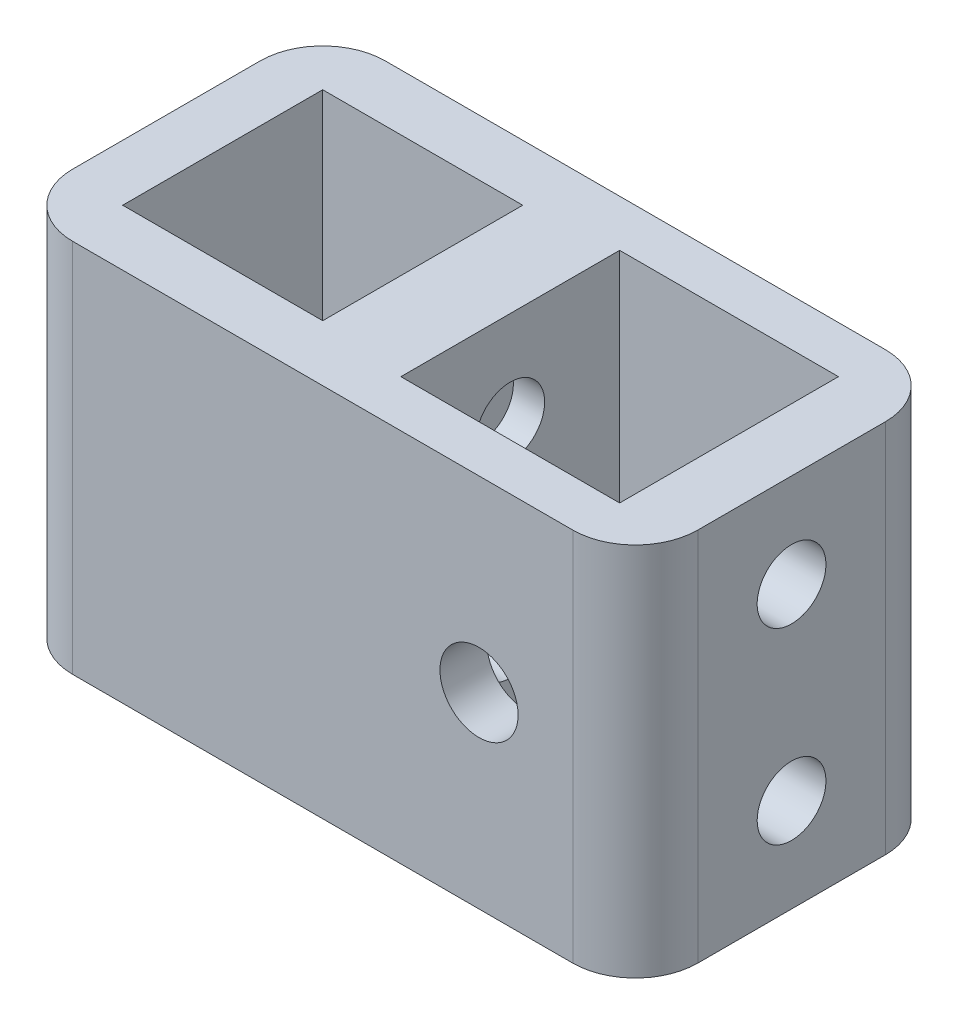
SolidWorks part; units mm, degrees
ref_plane "Front Plane" through (0, 0, 0) normal (0, 0, 1) x (1, 0, 0)
ref_plane "Top Plane" through (0, 0, 0) normal (0, 1, 0) x (1, 0, 0)
ref_plane "Right Plane" through (0, 0, 0) normal (1, 0, 0) x (0, 0, -1)
sketch "Sketch2" plane through (0, 0, 0) normal (0, 1, 0) x (1, 0, 0)
  line L1 (3.2, -3.2) -> (-3.2, -3.2)
  line L2 (3.2, -3.2) -> (3.2, 3.2)
  line L3 (3.2, 3.2) -> (-3.2, 3.2)
  line L4 (-3.2, -3.2) -> (-3.2, 3.2)
  line L5 (0, 3.2) -> (0, -3.2) construction
  line L6 (3.2, 0) -> (-3.2, 0) construction
  line L7 (5, -5) -> (-5, -5)
  line L8 (5, -5) -> (5, 5)
  line L9 (5, 5) -> (-5, 5)
  line L10 (-5, -5) -> (-5, 5)
  line L11 (0, 5) -> (0, -5) construction
  line L12 (5, 0) -> (-5, 0) construction
  line L13 (5, 5) -> (15, 5)
  line L14 (5, 5) -> (5, -5)
  line L15 (5, -5) -> (15, -5)
  line L16 (15, 5) -> (15, -5)
  circle A0 centre (0, 0) radius 2
  point P0 (0, 0)
  point P4 (0, 0)
  dimension "D5" = 4
  dimension "D1" = 6.4
  dimension "D2" = 6.4
  dimension "D3" = 10
  dimension "D4" = 10
  dimension "D6" = 10
extrude "Boss-Extrude1" add sketch "Sketch2" along normal blind 4 contours L4 L1 L2 L3 A0 | L10 L7 L8 L9 L1 L4 L3 L2 region at (0, 0, 3.1095) region at (0, 0, 4.8586)
extrude "Boss-Extrude2" add sketch "Sketch2<3>" along normal blind 12 contours L10 L7 L8 L9 L1 L4 L3 L2 region at (0, 0, 4.8586)
sketch "Sketch2<3>" plane through (0, 0, 0) normal (0, 1, 0) x (1, 0, 0) same geometry as "Sketch2"
extrude "Boss-Extrude3" add sketch "Sketch2<4>" along normal blind 12 contours L16 L13 L8 L15 region at (10, 0, 0)
sketch "Sketch2<4>" plane through (0, 0, 0) normal (0, 1, 0) x (1, 0, 0) same geometry as "Sketch2"
sketch "Sketch3" plane through (0, 0, 5) normal (0, 0, 1) x (1, 0, 0)
  line L0 (5, 12) -> (15, 12) construction
  line L1 (15, 12) -> (15, 0) construction
  line L2 (15, 0) -> (-5, 0) construction
  line L3 (15, 12) -> (15, 0) construction
  line L4 (15, 0) -> (5, 0) construction
  line L5 (5, 0) -> (5, 12) construction
  line L6 (5, 12) -> (15, 0) construction
  line L7 (15, 0) -> (10, 6) construction
  line L8 (10, 6) -> (9.7393, 12.9951) construction
  line L9 (10, 6) -> (15, 6) construction
  circle A2 centre (10, 6) radius 1.25
  dimension "D1" = 12
extrude "Cut-Extrude1" cut sketch "Sketch3" against normal blind 12
sketch "Sketch4" plane through (15, 0, 0) normal (1, 0, 0) x (0, 0, -1)
  line L0 (-5, 12) -> (5, 0) construction
  line L1 (5, 0) -> (5, 12) construction
  line L2 (5, 12) -> (-5, 0) construction
  line L3 (0, 6) -> (0, 12) construction
  line L4 (5, 12) -> (-5, 12) construction
  line L5 (0, 6) -> (1.8544, 6) construction
  circle A0 centre (0, 9) radius 1.1
  circle A1 centre (0, 3) radius 1.1
  point P17 (0, 0)
  point P20 (0.2129, 2.8011)
  dimension "D1" = 2.2
  dimension "D2" = 9
extrude "Cut-Extrude2" cut sketch "Sketch4" against normal blind 10
fillet "Fillet1" radius 2 4 edges at (-5, 6, 5) (-5, 6, -5) (15, 6, -5) (15, 6, 5)
sketch "Sketch5" plane through (0, 12, 0) normal (0, 1, 0) x (1, 0, 0)
  line L0 (13, 3) -> (13, -3) construction
  line L1 (13, 0) -> (3.2, 0) construction
  line L2 (3.2, -3.2) -> (3.2, 3.2) construction
  line L4 (-5, 3) -> (-5, -3)
  line L5 (-3, -5) -> (13, -5)
  line L6 (15, -3) -> (15, 3)
  line L7 (13, 5) -> (-3, 5)
  line L8 (-5, 3) -> (-5, -3)
  line L9 (-3, -5) -> (13, -5)
  line L10 (15, -3) -> (15, 3)
  line L11 (13, 5) -> (-3, 5)
  line L12 (6, -3.5) -> (13, -3.5)
  line L13 (6, -3.5) -> (6, 3.5)
  line L14 (6, 3.5) -> (13, 3.5)
  line L15 (13, -3.5) -> (13, 3.5)
  line L16 (9.5, 3.5) -> (9.5, -3.5) construction
  line L17 (6, 0) -> (13, 0) construction
  arc A4 (-5, -3) -> (-3, -5) centre (-3, -3) ccw
  arc A5 (13, -5) -> (15, -3) centre (13, -3) ccw
  arc A6 (15, 3) -> (13, 5) centre (13, 3) ccw
  arc A7 (-3, 5) -> (-5, 3) centre (-3, 3) ccw
  arc A8 (-5, -3) -> (-3, -5) centre (-3, -3) ccw
  arc A9 (13, -5) -> (15, -3) centre (13, -3) ccw
  arc A10 (15, 3) -> (13, 5) centre (13, 3) ccw
  arc A11 (-3, 5) -> (-5, 3) centre (-3, 3) ccw
  point P15 (9.5, 0)
  dimension "D2" = 7
  dimension "D3" = 7
  dimension "D1" = 0
extrude "Cut-Extrude3" cut sketch "Sketch5" against normal blind 14 contours L12 L15 L14 L13 region at (9.5, 12, 0)
